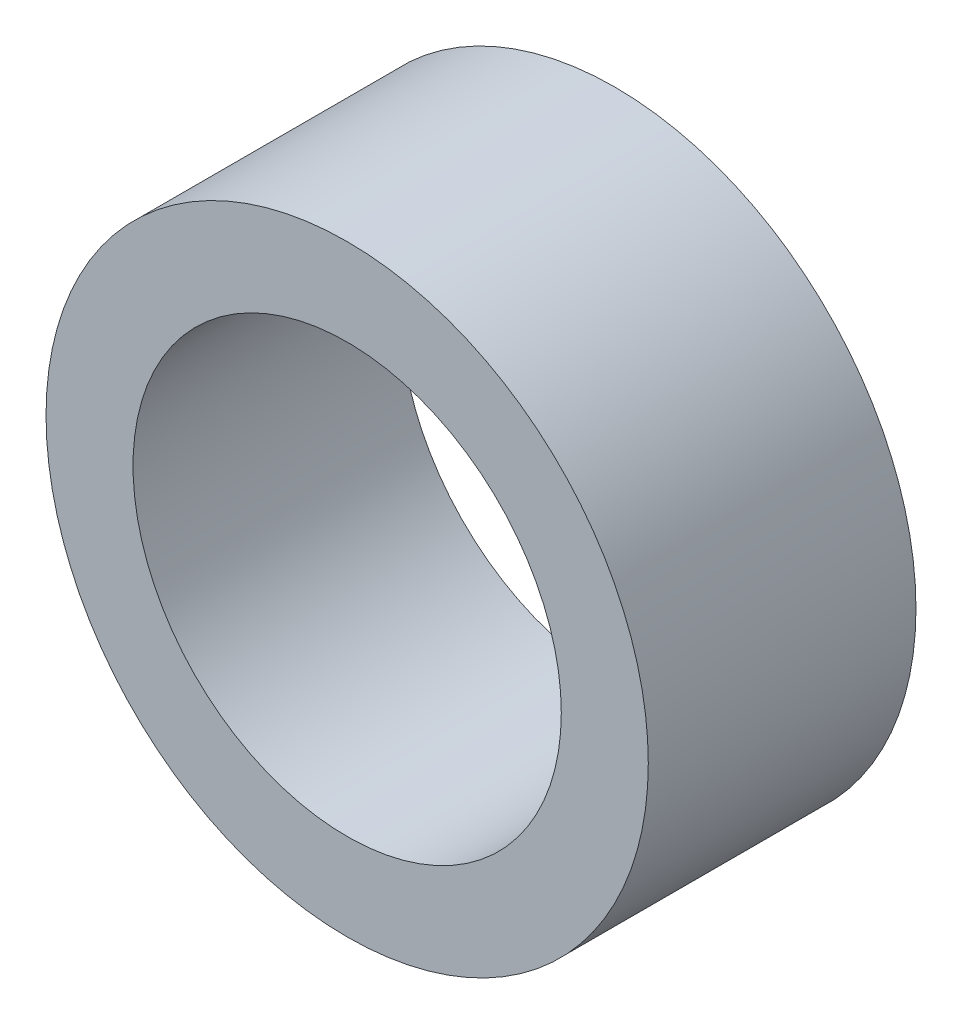
SolidWorks part; units mm, degrees
ref_plane "Front Plane" through (0, 0, 0) normal (0, 0, 1) x (1, 0, 0)
ref_plane "Top Plane" through (0, 0, 0) normal (0, 1, 0) x (1, 0, 0)
ref_plane "Right Plane" through (0, 0, 0) normal (1, 0, 0) x (0, 0, -1)
sketch "Sketch1" plane through (0, 0, 0) normal (0, 0, 1) x (1, 0, 0)
  circle A0 centre (0, 0) radius 2.25
  circle A1 centre (0, 0) radius 1.6
  dimension "OD" = 4.5
  dimension "ID" = 3.2
extrude "Extrude1" add sketch "Sketch1" along normal mid plane 2
sketch "Sketch2" plane through (0, 0, 0) normal (1, 0, 0) x (0, 0, -1)
  line L0 (-1, -1.6) -> (1, -1.6) construction
  line L3 (1, 1.6) -> (-1, 1.6) construction
  line L5 (-1, -1.6) -> (1, -1.6)
  line L6 (1, 1.6) -> (-1, 1.6)
sketch "Sketch4" plane through (0, 0, 1) normal (0, 0, 1) x (1, 0, 0)
  line L0 (0, 0) -> (-1.1314, 1.1314)
  line L1 (0, -1.1) -> (0, 1.1) construction
  circle A0 centre (0, 0) radius 1.6 construction
  dimension "D1" = 45
